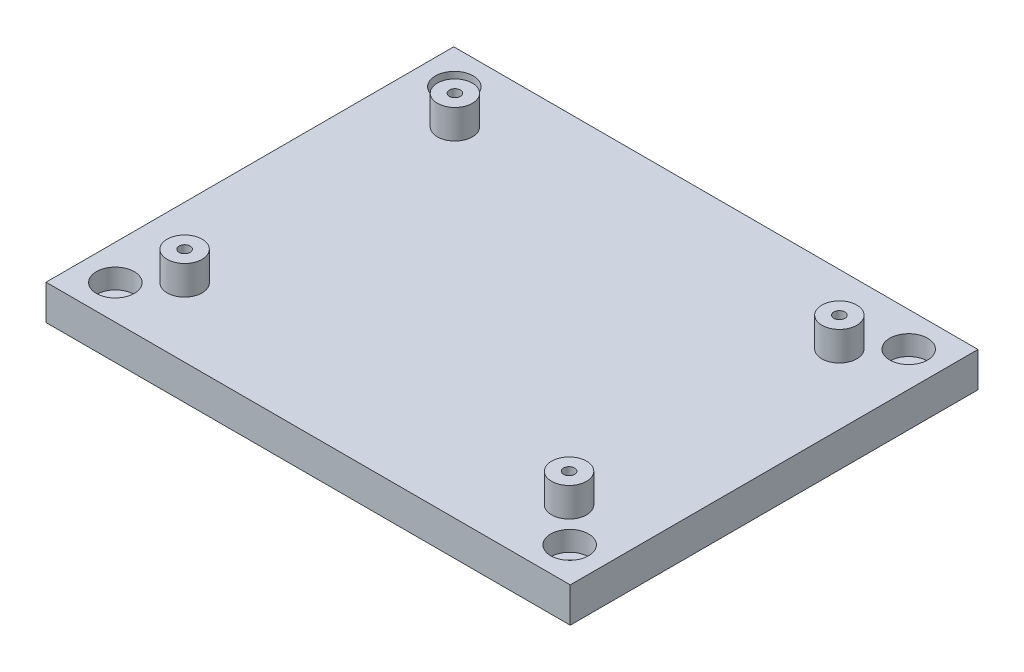
SolidWorks part; units mm, degrees
ref_plane "Front Plane" through (0, 0, 0) normal (0, 0, 1) x (1, 0, 0)
ref_plane "Top Plane" through (0, 0, 0) normal (0, 1, 0) x (1, 0, 0)
ref_plane "Right Plane" through (0, 0, 0) normal (1, 0, 0) x (0, 0, -1)
sketch "Szkic1" plane through (0, 0, 0) normal (0, 1, 0) x (1, 0, 0)
  line L0 (-45, -35) -> (45, 35) construction
  line L1 (-45, 35) -> (45, 35)
  line L2 (-45, 35) -> (-45, -35)
  line L3 (-45, -35) -> (45, -35)
  line L4 (45, 35) -> (45, -35)
  dimension "D1" = 70
  dimension "D2" = 90
extrude "Dodanie-wyciągnięcie1" add sketch "Szkic1" along normal blind 6
sketch "Szkic2" plane through (0, 6, 0) normal (0, 1, 0) x (1, 0, 0)
  circle A0 centre (-33, 23.2) radius 3
  circle A1 centre (-33, -23.2) radius 3
  circle A2 centre (33, -23.2) radius 3
  circle A3 centre (33, 23.2) radius 3
  circle A4 centre (33, 23.2) radius 0.95
  circle A5 centre (-33, 23.2) radius 0.95
  circle A6 centre (-33, -23.2) radius 0.95
  circle A7 centre (33, -23.2) radius 0.95
  dimension "D1" = 6
  dimension "D2" = 1.9
extrude "Dodanie-wyciągnięcie2" add sketch "Szkic2" along normal blind 5
hole_wizard "CBORE for M3 Hex Socket Head Cap Screw1" positions "Szkic3" profile "Szkic4" counterbore size "M3" standard "DIN"
sketch "Szkic3" plane through (0, 6, 0) normal (0, 1, 0) x (1, 0, 0)
  line L2 (-33, 23.2) -> (-45, 35) construction
  line L5 (33, -23.2) -> (45, -35) construction
  point P0 (-39, 29.1)
  point P2 (-39, -29.1)
  point P4 (39, 29.1)
  point P6 (39, -29.1)
sketch "Szkic4" plane through (-39, 6, -29.1) normal (1, 0, 0) x (0, 0, 1)
  line L0 (0, 0) -> (0, 18.6614)
  line L1 (0, 18.6614) -> (1.6, 17.7)
  line L2 (1.6, 17.7) -> (1.6, 3.4)
  line L3 (1.6, 3.4) -> (3.25, 3.4)
  line L4 (3.25, 3.4) -> (3.25, 0)
  line L5 (3.25, 0) -> (0, 0)
  line L10 (0, 18.6614) -> (-1.6, 17.7) construction
  line L11 (0, -6.35) -> (0, 107.95) construction
  dimension "Hole Dia." = 3.2
  dimension "Hole Depth" = 17.7
  dimension "C'Bore Dia." = 6.5
  dimension "C'Bore Depth" = 3.4
  dimension "Drill Angle" = 118
